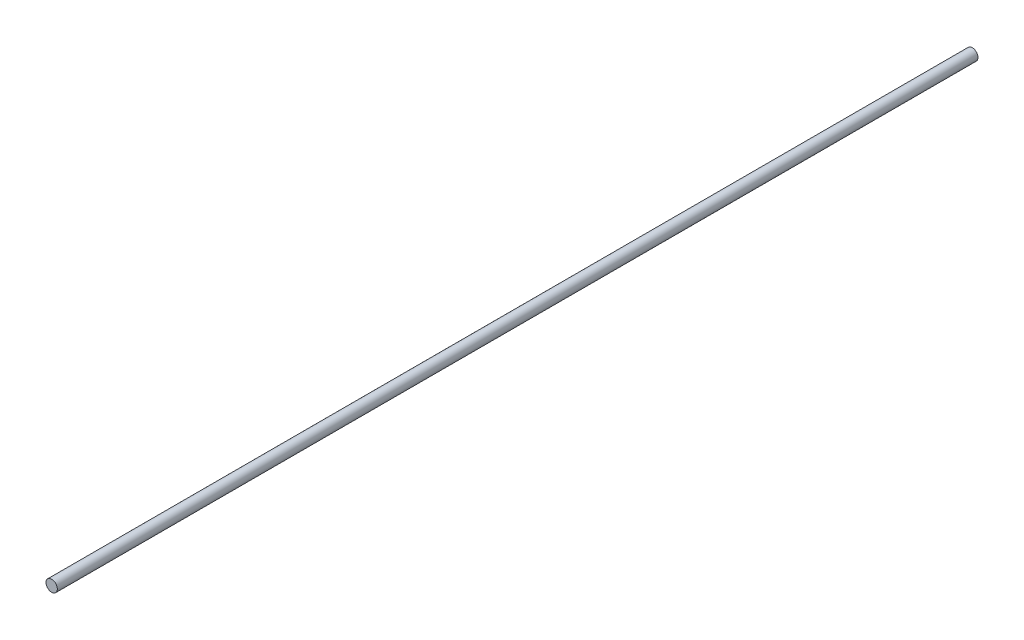
SolidWorks part; units mm, degrees
material "A286, generico"
ref_plane "Piano frontale" through (0, 0, 0) normal (0, 0, 1) x (1, 0, 0)
ref_plane "Piano superiore" through (0, 0, 0) normal (0, 1, 0) x (1, 0, 0)
ref_plane "Piano destro" through (0, 0, 0) normal (1, 0, 0) x (0, 0, -1)
sketch "Schizzo1" plane through (0, 0, 0) normal (0, 0, 1) x (1, 0, 0)
  circle A0 centre (0, 0) radius 2
  dimension "D1" = 4
extrude "Estrusione-Estrusione1" add sketch "Schizzo1" along normal blind 162 and the other way blind 162
